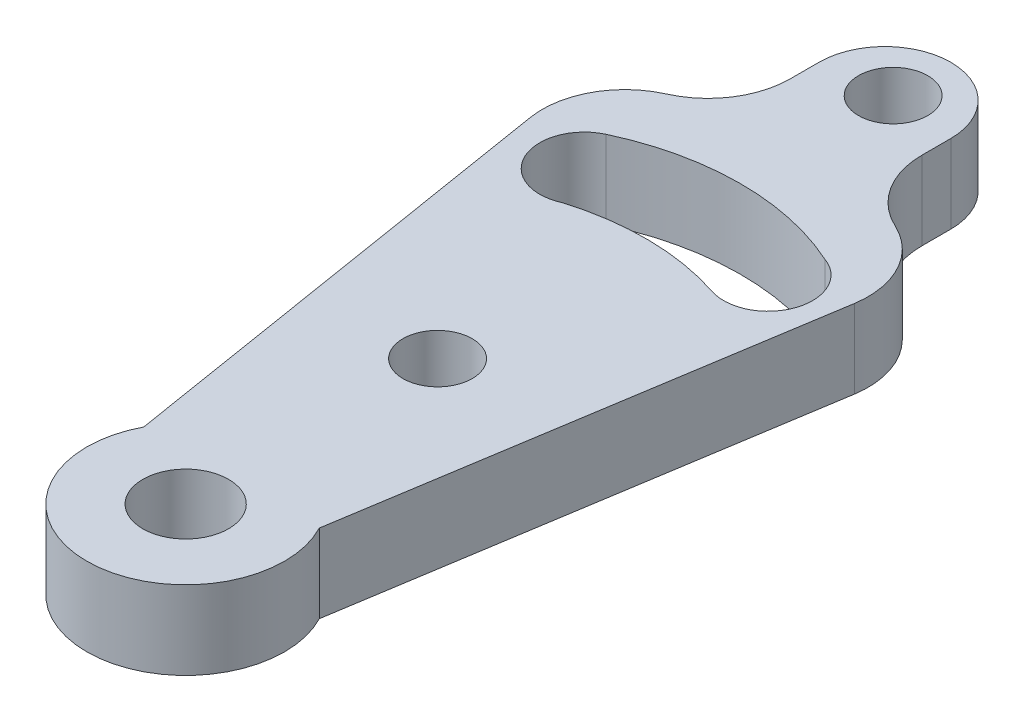
SolidWorks part; units mm, degrees
note: '?' marks a value the reader was unsure of.
ref_plane "Front Plane" through (0, 0, 0) normal (0, 0, 1) x (1, 0, 0)
ref_plane "Top Plane" through (0, 0, 0) normal (0, 1, 0) x (1, 0, 0)
ref_plane "Right Plane" through (0, 0, 0) normal (1, 0, 0) x (0, 0, -1)
ref_plane "Plane1" through (0, 2274.8614, 0) normal (0, -1, 0) x (1, 0, 0)
sketch "Sketch11" plane through (0, 2274.8614, 0) normal (0, -1, 0) x (1, 0, 0)
  line L0 (-14.8483, -526.6638) -> (-14.8483, -524.9224)
  line L1 (-9.1074, -515.0651) -> (-13.5369, -487.0545)
  line L2 (-24.1679, -487.0386) -> (-28.7032, -515.011)
  line L3 (-22.8483, -524.9407) -> (-22.8483, -526.6638)
  arc A0 (-14.8483, -524.9224) -> (-11.9472, -520.3843) centre (-9.8483, -524.9224) cw
  arc A1 (-11.9472, -520.3843) -> (-9.1074, -515.0651) centre (-14.046, -515.8461) ccw
  arc A2 (-13.5369, -487.0545) -> (-24.1679, -487.0386) centre (-18.8483, -484.2635) ccw
  arc A3 (-28.7032, -515.011) -> (-25.808, -520.3759) centre (-23.7676, -515.8112) ccw
  arc A4 (-25.808, -520.3759) -> (-22.8483, -524.9407) centre (-27.8483, -524.9407) cw
  arc A5 (-22.8483, -526.6638) -> (-14.8483, -526.6638) centre (-18.8483, -526.6638) ccw
base flange "Base-Flange1" sketch "Sketch11" thickness 4.7625 reverse thickness direction yes parameters "D1"=0
sketch "Sketch16" plane through (0, 2279.6239, 0) normal (0, 1, 0) x (-1, 0, 0)
  arc A0 (23.2329, -511.5196) -> (14.1042, -511.4068) centre (18.8483, -496.9135) cw
  arc A1 (14.1042, -511.4068) -> (12.3345, -516.5034) centre (13.2193, -513.9551) ccw
  arc A2 (12.3345, -516.5034) -> (25.5319, -516.4251) centre (18.8483, -502.1635) ccw
  arc A3 (25.5319, -516.4251) -> (23.2329, -511.5196) centre (24.3824, -513.9723) ccw
extrude "Cut-Extrude1" cut sketch "Sketch16" against normal through all
hole_wizard "Ø5.2 (5.2) Diameter Hole1" positions "Sketch18" profile "Sketch17" hole size "Ø5.2" standard "ANSI Metric"
sketch "Sketch18" plane through (0, 2279.6239, 0) normal (0, 1, 0) x (1, 0, 0)
  point P0 (-18.8483, 484.2635)
sketch "Sketch17" plane through (-18.8483, 2279.6239, -484.2635) normal (1, 0, 0) x (0, 0, 1)
  line L0 (0, 0) -> (0, 4.7625)
  line L1 (0, 4.7625) -> (2.6, 4.7625)
  line L2 (2.6, 4.7625) -> (2.6, 0)
  line L5 (2.6, 0) -> (0, 0)
  line L11 (0, -6.35) -> (0, 107.95) construction
  dimension "Thru Hole Dia." = 5.2
  dimension "Thru Hole Depth" = 4.7625
hole_wizard "Ø4.2 (4.2) Diameter Hole1" positions "Sketch20" profile "Sketch19" hole size "Ø4.2" standard "ANSI Metric"
sketch "Sketch20" plane through (0, 2279.6239, 0) normal (0, 1, 0) x (1, 0, 0)
  point P0 (-18.8483, 499.5385)
  point P1 (-18.8483, 527.1638)
sketch "Sketch19" plane through (-18.8483, 2279.6239, -499.5385) normal (1, 0, 0) x (0, 0, 1)
  line L0 (0, 0) -> (0, 4.7625)
  line L1 (0, 4.7625) -> (2.1, 4.7625)
  line L2 (2.1, 4.7625) -> (2.1, 0)
  line L5 (2.1, 0) -> (0, 0)
  line L11 (0, -6.35) -> (0, 107.95) construction
  dimension "Thru Hole Dia." = 4.2
  dimension "Thru Hole Depth" = 4.7625
ref_point "Point1"
ref_axis "Axis1" through (-18.8483, 2274.8614, -484.2635) along (0, 1, 0)?
ref_axis "Axis2" through (-18.8483, 2274.8614, -499.5385) along (0, 1, 0)?
ref_axis "Axis3" through (-18.8483, 2274.8614, -527.1638) along (0, 1, 0)?
sketch "Bend-Lines4" plane through (0, 0, 0) normal (0, 1, 0) x (1, 0, 0)
sketch "Bounding-Box4" plane through (0, 0, 0) normal (0, 1, 0) x (1, 0, 0)
sheet metal parameters "Sheet-Metal(5)" thickness 4.7625 parameters "D1"=0
flat pattern "Flat-Pattern(5)" [suppressed]
sketch "Bend-Lines5" plane through (0, 0, 0) normal (0, 1, 0) x (1, 0, 0)
sketch "Bounding-Box5" [suppressed] plane through (0, 0, 0) normal (0, 1, 0) x (1, 0, 0)
sheet metal parameters "Sheet-Metal(6)" thickness 4.7625 parameters "D1"=0
flat pattern "Flat-Pattern(5)"
sketch "Bend-Lines5" plane through (0, 0, 0) normal (0, 1, 0) x (1, 0, 0)
sketch "Bounding-Box5" [suppressed] plane through (0, 0, 0) normal (0, 1, 0) x (1, 0, 0)
sheet metal parameters "Sheet-Metal(7)" thickness 4.7625 parameters "D1"=0
flat pattern "Flat-Pattern(5)"
sketch "Bend-Lines5" plane through (0, 0, 0) normal (0, 1, 0) x (1, 0, 0)
sketch "Bounding-Box5" [suppressed] plane through (0, 0, 0) normal (0, 1, 0) x (1, 0, 0)
sheet metal parameters "Sheet-Metal(8)" thickness 4.7625 parameters "D1"=0
flat pattern "Flat-Pattern(5)"
sketch "Bend-Lines5" plane through (0, 0, 0) normal (0, 1, 0) x (1, 0, 0)
sketch "Bounding-Box5" [suppressed] plane through (0, 0, 0) normal (0, 1, 0) x (1, 0, 0)
